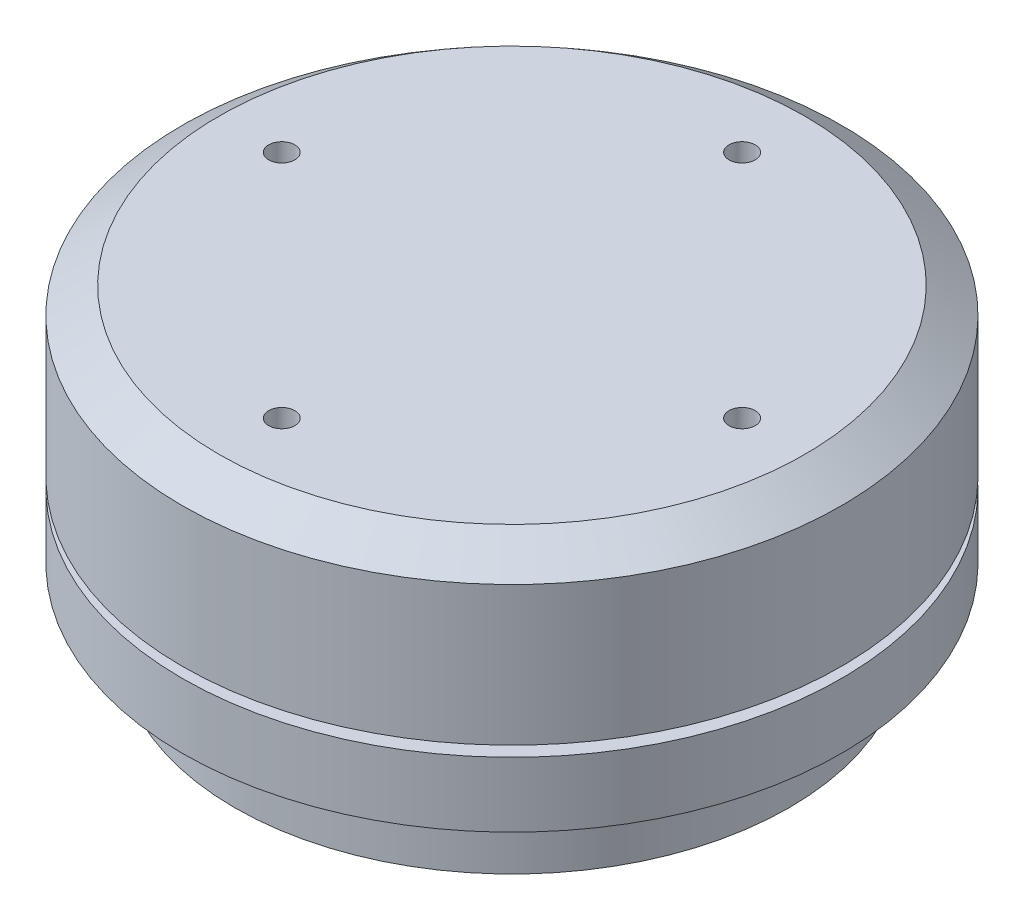
SolidWorks part; units mm, degrees
ref_plane "Спереди" through (0, 0, 0) normal (0, 0, 1) x (1, 0, 0)
ref_plane "Сверху" through (0, 0, 0) normal (0, 1, 0) x (1, 0, 0)
ref_plane "Справа" through (0, 0, 0) normal (1, 0, 0) x (0, 0, -1)
ref_axis "Axis1" through (0, 0, 0) along (0, 1, 0)
sketch "Sketch1" plane through (0, 0, 0) normal (0, 0, 1) x (1, 0, 0)
  line L0 (0, 0) -> (0, -78619.6517) construction
  line L1 (0, 0) -> (0, 30)
  line L2 (0, 30) -> (-28, 30)
  line L3 (-28, 30) -> (-31.5, 27.5)
  line L4 (-31.5, 27.5) -> (-31.5, 14.2)
  line L5 (-31.5, 14.2) -> (-29.5, 14.2)
  line L6 (-29.5, 14.2) -> (-29.5, 13.2)
  line L7 (-29.5, 13.2) -> (-31.5, 13.2)
  line L8 (-31.5, 13.2) -> (-31.5, 7)
  line L9 (-31.5, 7) -> (-26.5, 5.6)
  line L10 (-26.5, 5.6) -> (-26.5, 0)
  line L11 (-26.5, 0) -> (0, 0)
  point P11 (-29.5, 12.4443)
  point P15 (-31.5, 8.1021)
  dimension "D1" = 56
  dimension "D2" = 63
  dimension "D3" = 2.5
  dimension "D4" = 1.4
  dimension "D5" = 53
  dimension "D6" = 1
  dimension "D7" = 2
  dimension "D8" = 30
  dimension "D9" = 6.2
  dimension "D10" = 5.6
revolve "Revolve1" add sketch "Sketch1" angle 360 about L0
hole_wizard "M3x0.5 Tapped Hole1" positions "Sketch2" profile "Sketch3" tap size "M3x0.5" standard "ANSI Metric"
sketch "Sketch2" plane through (0, 30, 0) normal (0, 1, 0) x (1, 0, 0)
  circle A0 centre (0, 0) radius 22 construction
  point P0 (0, 22)
  point P39 (0, -22)
  point P44 (22, 0)
  point P69 (-22, 0)
sketch "Sketch3" plane through (0, 30, -22) normal (1, 0, 0) x (0, 0, 1)
  line L0 (0, 0) -> (0, 6.7511)
  line L1 (0, 6.7511) -> (1.25, 6)
  line L2 (1.25, 6) -> (1.25, 0)
  line L5 (1.25, 0) -> (0, 0)
  line L10 (0, 6.7511) -> (-1.25, 6) construction
  line L11 (0, -6.35) -> (0, 107.95) construction
  dimension "Tap Drill Dia." = 2.5
  dimension "Tap Drill Depth" = 6
  dimension "Drill Angle" = 118
cosmetic thread "Hole Thread1" parameters "D1"=6, "D2"=3
cosmetic thread "Hole Thread2" parameters "D1"=6, "D2"=3
cosmetic thread "Hole Thread3" parameters "D1"=6, "D2"=3
cosmetic thread "Hole Thread5" parameters "D1"=6, "D2"=3
hole_wizard "M3x0.5 Tapped Hole2" positions "Sketch4" profile "Sketch5" tap size "M3x0.5" standard "ANSI Metric"
sketch "Sketch4" plane through (0, 0, 0) normal (0, -1, 0) x (-1, 0, 0)
  circle A0 centre (0, 0) radius 15 construction
  point P2 (0, 15)
  point P40 (0, -15)
  point P45 (15, 0)
  point P54 (-15, 0)
  dimension "D1" = 30
sketch "Sketch5" plane through (0, 0, -15) normal (1, 0, 0) x (0, 0, -1)
  line L0 (0, 0) -> (0, 9.2511)
  line L1 (0, 9.2511) -> (1.25, 8.5)
  line L2 (1.25, 8.5) -> (1.25, 0)
  line L5 (1.25, 0) -> (0, 0)
  line L10 (0, 9.2511) -> (-1.25, 8.5) construction
  line L11 (0, -6.35) -> (0, 107.95) construction
  dimension "Tap Drill Dia." = 2.5
  dimension "Tap Drill Depth" = 8.5
  dimension "Drill Angle" = 118
cosmetic thread "Hole Thread8" parameters "D1"=6, "D2"=3
cosmetic thread "Hole Thread9" parameters "D1"=6, "D2"=3
cosmetic thread "Hole Thread11" parameters "D1"=6, "D2"=3
cosmetic thread "Hole Thread13" parameters "D1"=6, "D2"=3
